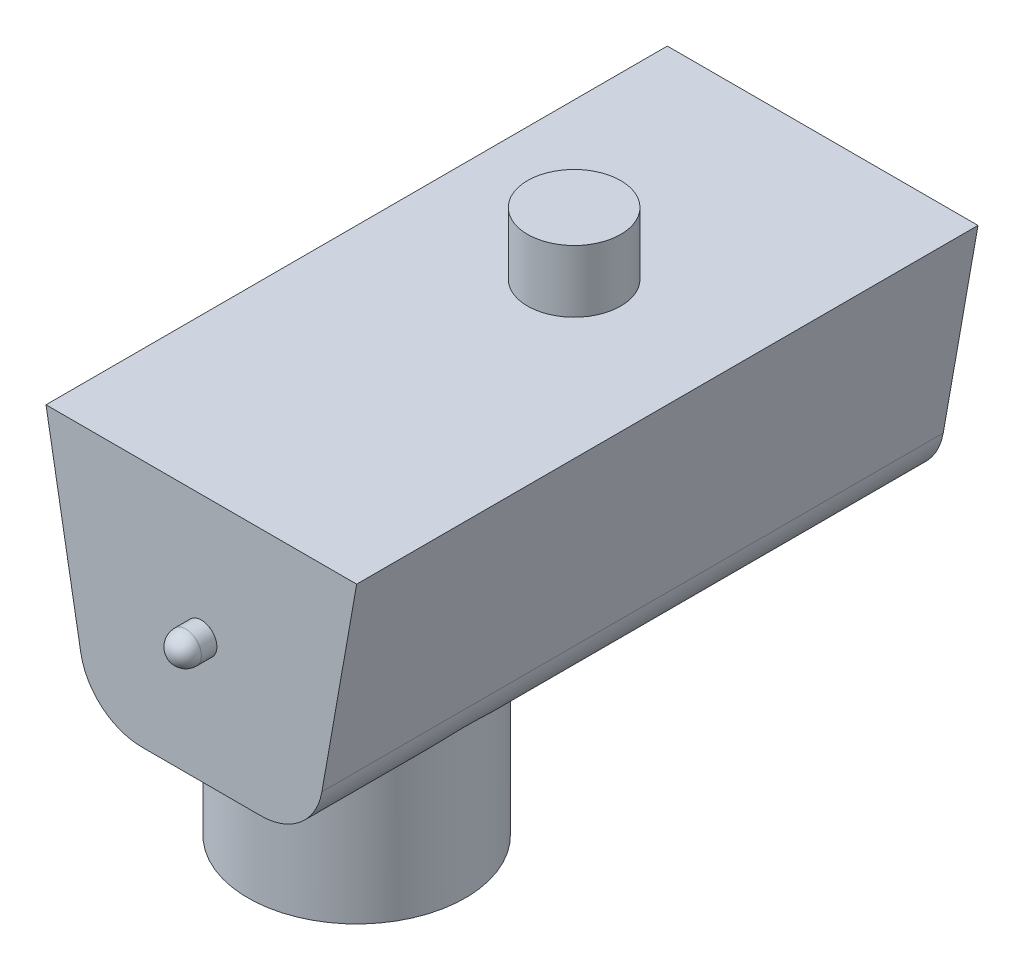
SolidWorks part; units mm, degrees
ref_plane "Front Plane" through (0, 0, 0) normal (0, 0, 1) x (1, 0, 0)
ref_plane "Top Plane" through (0, 0, 0) normal (0, 1, 0) x (1, 0, 0)
ref_plane "Right Plane" through (0, 0, 0) normal (1, 0, 0) x (0, 0, -1)
sketch "Sketch1" plane through (0, 0, 0) normal (0, 0, 1) x (1, 0, 0)
  line L0 (-5, 0) -> (5, 0)
  line L1 (-5, 0) -> (-3.8808, -6.3473)
  line L2 (-1.9112, -8) -> (1.9112, -8)
  line L3 (3.8808, -6.3473) -> (5, 0)
  arc A0 (1.9112, -8) -> (3.8808, -6.3473) centre (1.9112, -6) ccw
  arc A1 (-3.8808, -6.3473) -> (-1.9112, -8) centre (-1.9112, -6) ccw
  circle A2 centre (0, -4) radius 0.5
  point P4 (0, 0)
  dimension "D5" = 2
  dimension "D6" = 1
  dimension "D1" = 10
  dimension "D2" = 80
  dimension "D3" = 80
  dimension "D4" = 8
  dimension "D7" = 5
  dimension "D8" = 4
extrude "Boss-Extrude1" add sketch "Sketch1" against normal blind 20
extrude "Boss-Extrude2" add sketch "Sketch1<2>" along normal blind 1 separate body contours A2 region at (0, -4, 0)
sketch "Sketch1<2>" plane through (0, 0, 0) normal (0, 0, 1) x (1, 0, 0) same geometry as "Sketch1"
fillet "Fillet1" radius 0.5 1 edges at (0.5, -4, 1)
sketch "Sketch2" plane through (0, -8, 0) normal (0, -1, 0) x (1, 0, 0)
  line L1 (-1.9112, -20) -> (1.9112, -20) construction
  circle A0 centre (0, -5) radius 3.5
  circle A1 centre (0, -5) radius 3
  point P3 (0, 0)
  dimension "D1" = 7
  dimension "D2" = 6
  dimension "D3" = 15
extrude "Boss-Extrude3" add sketch "Sketch2" along normal blind 4 and the other way blind 2
sketch "Sketch3" plane through (0, 0, 0) normal (0, 1, 0) x (1, 0, 0)
  line L0 (5, 20) -> (-5, 20) construction
  circle A0 centre (0, 12) radius 1.5
  point P4 (0, 0)
  dimension "D1" = 3
  dimension "D2" = 8
extrude "Boss-Extrude4" add sketch "Sketch3" along normal blind 2
